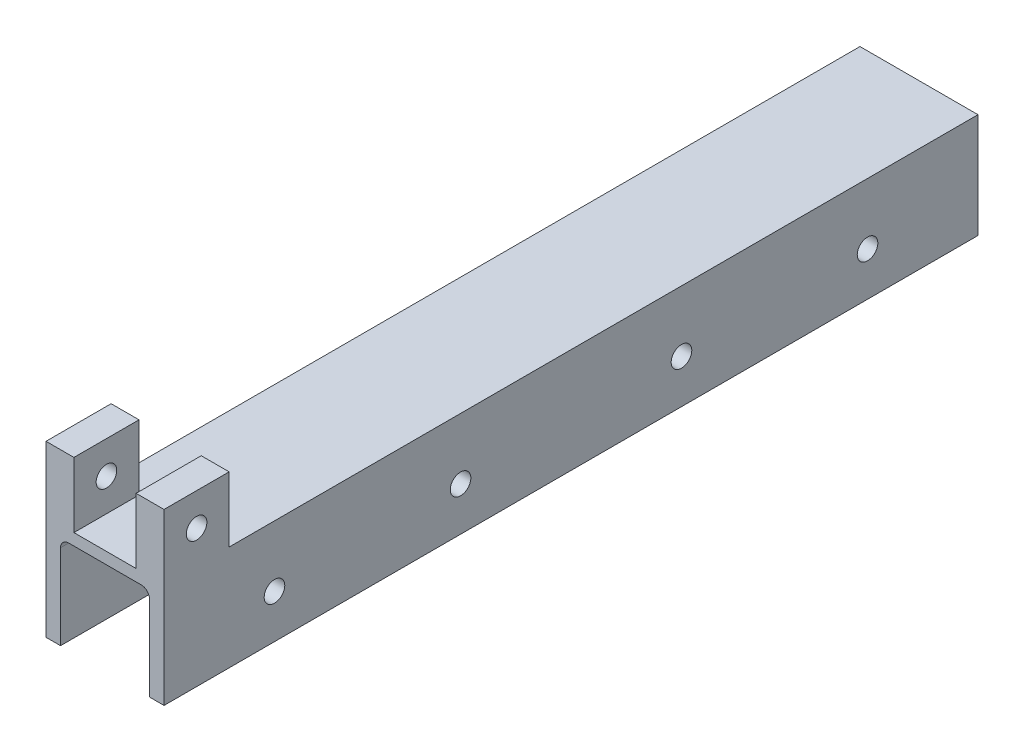
SolidWorks part; units mm, degrees
ref_plane "Front Plane" through (0, 0, 0) normal (0, 0, 1) x (1, 0, 0)
ref_plane "Top Plane" through (0, 0, 0) normal (0, 1, 0) x (1, 0, 0)
ref_plane "Right Plane" through (0, 0, 0) normal (1, 0, 0) x (0, 0, -1)
sketch "Sketch2" plane through (0, 0, 0) normal (0, 0, 1) x (1, 0, 0)
  line L0 (319.8414, 0) -> (-319.8414, 0) construction
  line L2 (0, 0) -> (0, 22.86)
  line L3 (0, 22.86) -> (25.781, 22.86)
  line L4 (25.781, 0) -> (25.781, 22.86)
  line L44 (22.606, 18.542) -> (22.606, 0)
  line L47 (3.175, 0) -> (3.175, 18.542)
  line L48 (4.953, 20.32) -> (20.828, 20.32)
  line L49 (0, 0) -> (3.175, 0)
  line L50 (22.606, 0) -> (25.781, 0)
  arc A0 (22.606, 18.542) -> (20.828, 20.32) centre (20.828, 18.542) ccw
  arc A1 (3.175, 18.542) -> (4.953, 20.32) centre (4.953, 18.542) cw
  point P15 (3.175, 20.32)
  point P16 (3.175, 20.32)
  dimension "D6" = 1.778
  dimension "D1" = 22.86
  dimension "D2" = 25.781
  dimension "D3" = 3.175
  dimension "D4" = 19.431
  dimension "D5" = 3.175
  dimension "D7" = 20.32
extrude "Boss-Extrude2" add sketch "Sketch2" against normal blind 177.8
sketch "Sketch19" plane through (0, 0, 0) normal (1, 0, 0) x (0, 0, -1)
  line L0 (0, 265.0009) -> (0, -265.0009) construction
  line L1 (319.8414, 0) -> (-319.8414, 0) construction
  line L2 (0, 20.32) -> (177.8, 20.32) construction
  line L3 (0, 0) -> (88.9, 0) construction
  line L4 (177.8, 0) -> (0, 0) construction
  line L5 (88.9, 0) -> (88.9, 22.86) construction
  line L6 (177.8, 22.86) -> (0, 22.86) construction
  line L7 (177.8, 0) -> (177.8, 22.86) construction
  circle A0 centre (24.13, 9.525) radius 2.2479
  circle A1 centre (64.77, 9.525) radius 2.2479
  circle A2 centre (113.03, 9.525) radius 2.2479
  circle A3 centre (153.67, 9.525) radius 2.2479
  dimension "D2" = 4.4958
  dimension "D5" = 4.4958
  dimension "D9" = 24.13
  dimension "D14" = 4.4958
  dimension "D1" = 24.13
  dimension "D3" = 9.525
  dimension "D4" = 40.64
  dimension "D6" = 9.525
  dimension "D7" = 24.13
  dimension "D8" = 88.9
  dimension "D10" = 40.64
  dimension "D11" = 24.13
  dimension "D12" = 2.54
  dimension "D13" = 20.32
extrude "Cut-Extrude3" cut sketch "Sketch19" along normal through all
sketch "Sketch21" plane through (0, 22.86, 0) normal (0, 1, 0) x (1, 0, 0)
  line L0 (12.8905, 0) -> (12.8905, 177.8) construction
  line L1 (0, 0) -> (25.781, 0) construction
  line L2 (0, 0) -> (6.096, 0)
  line L3 (0, 0) -> (0, 14.224)
  line L4 (0, 14.224) -> (6.096, 14.224)
  line L5 (6.096, 0) -> (6.096, 14.224)
  line L6 (25.781, 177.8) -> (0, 177.8) construction
  line L7 (0, 0) -> (6.096, 0) construction
  line L8 (6.096, 0) -> (6.096, 6.5548) construction
  line L10 (19.685, 0) -> (19.685, 6.5548) construction
  line L11 (25.781, 0) -> (19.685, 0)
  line L12 (25.781, 0) -> (25.781, 14.224)
  line L13 (25.781, 14.224) -> (19.685, 14.224)
  line L14 (19.685, 0) -> (19.685, 14.224)
  dimension "D1" = 6.096
  dimension "D2" = 6.096
  dimension "D3" = 14.224
  dimension "D4" = 13.589
  dimension "D5" = 6.096
  dimension "D6" = 6.096
  dimension "D7" = 14.224
extrude "Boss-Extrude4" add sketch "Sketch21" along normal blind 14.224
sketch "Sketch22" plane through (19.685, 0, 0) normal (-1, 0, 0) x (0, 0, 1)
  line L0 (0, 37.084) -> (-14.224, 37.084) construction
  line L1 (0, -265.0009) -> (0, 265.0009) construction
  line L2 (-14.224, 22.86) -> (0, 22.86) construction
  line L3 (-7.112, 22.86) -> (-7.112, 29.972) construction
  line L4 (-177.8, 0) -> (0, 0) construction
  circle A0 centre (-7.112, 29.972) radius 2.2479
  point P4 (-7.112, 37.084)
  dimension "D1" = 4.4958
  dimension "D2" = 7.112
  dimension "D3" = 7.112
  dimension "D4" = 14.224
  dimension "D5" = 7.112
  dimension "D6" = 29.972
extrude "Cut-Extrude4" cut sketch "Sketch22" against normal through all both and the other way through all
